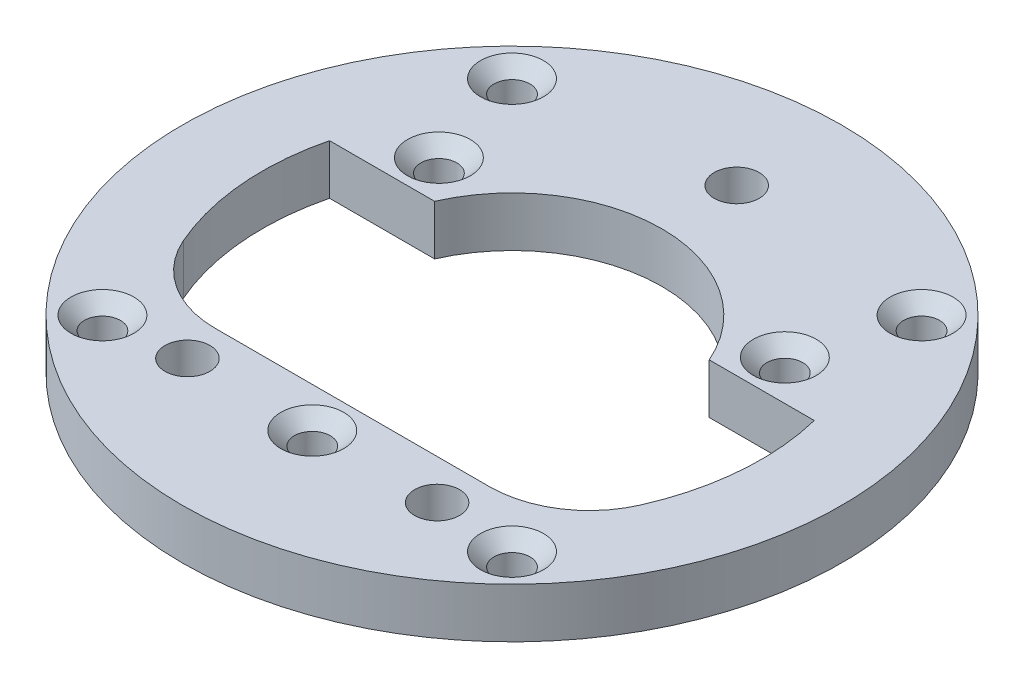
SolidWorks part; units mm, degrees
material "ABS"
ref_plane "Front Plane" through (0, 0, 0) normal (0, 0, 1) x (1, 0, 0)
ref_plane "Top Plane" through (0, 0, 0) normal (0, 1, 0) x (1, 0, 0)
ref_plane "Right Plane" through (0, 0, 0) normal (1, 0, 0) x (0, 0, -1)
sketch "Sketch1" plane through (0, 0, 0) normal (0, 1, 0) x (1, 0, 0)
  circle A0 centre (0, 0) radius 33
  circle A1 centre (0, 0) radius 25
  dimension "D1" = 66
  dimension "D2" = 8
extrude "Boss-Extrude1" add sketch "Sketch1" along normal blind 5
sketch "Sketch2" plane through (0, 5, 0) normal (0, 1, 0) x (1, 0, 0)
  line L0 (-19.2094, -16) -> (19.2094, -16)
  line L1 (-24.2693, 6) -> (-13.7477, 6)
  line L2 (0, 0) -> (7.7557, 0) construction
  line L3 (13.7477, 6) -> (24.2693, 6)
  line L4 (-20.5061, 20.5061) -> (0, 0) construction
  circle A0 centre (0, 22.5) radius 2.25 construction
  circle A1 centre (-12.5, -20) radius 2.25 construction
  circle A2 centre (12.5, -20) radius 2.25 construction
  circle A3 centre (0, -20) radius 1.5 construction
  circle A4 centre (0, 0) radius 20 construction
  circle A5 centre (-17.3205, 10) radius 1.5 construction
  circle A6 centre (0, 0) radius 25 construction
  circle A7 centre (17.3205, 10) radius 1.5 construction
  arc A8 (-13.7477, 6) -> (13.7477, 6) centre (0, 0) cw
  arc A9 (24.2693, 6) -> (-24.2882, 5.9232) centre (0, 0) ccw
  arc A10 (19.2094, -16) -> (-19.2094, -16) centre (0, 0) cw
  circle A12 centre (0, 0) radius 29 construction
  circle A13 centre (0, 0) radius 33 construction
  circle A14 centre (-20.5061, 20.5061) radius 1.75 construction
  circle A15 centre (20.5061, 20.5061) radius 1.75 construction
  circle A16 centre (20.5061, -20.5061) radius 1.75 construction
  circle A17 centre (-20.5061, -20.5061) radius 1.75 construction
  point P19 (0, 0)
  point P44 (0, 0)
  circle M2 centre (0, 0) radius 25
  dimension "D5" = 4.5
  dimension "D6" = 4.5
  dimension "D7" = 4.5
  dimension "D10" = 3
  dimension "D12" = 15
  dimension "D16" = 3.5
  dimension "D1" = 25
  dimension "D2" = 12.5
  dimension "D3" = 22.5
  dimension "D4" = 20
  dimension "D9" = 5
  dimension "D11" = 4
  dimension "D13" = 4
  dimension "D14" = 4
  dimension "D15" = 135
  dimension "D18" = 5
  dimension "D8" = 3
  dimension "D17" = 4
extrude "Saliente-Extruir1" add sketch "Sketch2" against normal up to surface (5 mm away) contours L1 A8 L3 M2 | L0 M2 region at (0, 5, 19.6621) region at (0, 5, -15.401) up to face at (0, 0, 33)
sketch "Croquis1" plane through (0, 5, 0) normal (0, 1, 0) x (1, 0, 0)
  circle A0 centre (-20.5061, 20.5061) radius 1.75 construction
  circle A1 centre (-20.5061, 20.5061) radius 1.75
  circle A2 centre (0, 22.5) radius 2.25 construction
  circle A3 centre (0, 22.5) radius 2.25
  circle A4 centre (20.5061, 20.5061) radius 1.75 construction
  circle A5 centre (20.5061, 20.5061) radius 1.75
  circle A6 centre (-17.3205, 10) radius 1.5 construction
  circle A7 centre (-17.3205, 10) radius 1.5
  circle A8 centre (17.3205, 10) radius 1.5 construction
  circle A9 centre (17.3205, 10) radius 1.5
  circle A10 centre (0, -20) radius 1.5 construction
  circle A11 centre (0, -20) radius 1.5
  circle A12 centre (12.5, -20) radius 2.25 construction
  circle A13 centre (12.5, -20) radius 2.25
  circle A14 centre (-12.5, -20) radius 2.25 construction
  circle A15 centre (-12.5, -20) radius 2.25
  circle A16 centre (-20.5061, -20.5061) radius 1.75 construction
  circle A17 centre (-20.5061, -20.5061) radius 1.75
  circle A18 centre (20.5061, -20.5061) radius 1.75 construction
  circle A19 centre (20.5061, -20.5061) radius 1.75
extrude "Cortar-Extruir1" cut sketch "Croquis1" against normal up to next
fillet "Redondeo1" radius 10 2 edges at (19.2094, 2.5, 16) (-19.2094, 2.5, 16)
hole_wizard "CSK for M3 Flat Head Machine Screw1" positions "Sketch4" profile "Sketch5" countersink size "M3" standard "ANSI Metric" end condition through all
sketch "Sketch4" plane through (0, 5, 0) normal (0, 1, 0) x (1, 0, 0)
  point P0 (-20.5061, 20.5061)
  point P3 (20.5061, 20.5061)
  point P6 (20.5061, -20.5061)
  point P9 (-20.5061, -20.5061)
sketch "Sketch5" plane through (-20.5061, 5, -20.5061) normal (1, 0, 0) x (0, 0, 1)
  line L0 (0, 0) -> (0, 5)
  line L1 (0, 5) -> (1.8, 5)
  line L2 (1.8, 5) -> (1.8, 1.35)
  line L3 (1.8, 1.35) -> (3.15, 0)
  line L5 (3.15, 0) -> (0, 0)
  line L6 (-1.8, 1.35) -> (-3.15, 0) construction
  line L11 (0, -6.35) -> (0, 107.95) construction
  dimension "Thru Hole Dia." = 3.6
  dimension "Thru Hole Depth" = 5
  dimension "Near C'Sink Dia." = 6.3
  dimension "Near C'Sink Angle" = 90
hole_wizard "CSK for M3 Flat Head Machine Screw2" positions "Sketch6" profile "Sketch7" countersink size "M3" standard "ANSI Metric" end condition through all
sketch "Sketch6" plane through (0, 5, 0) normal (0, 1, 0) x (1, 0, 0)
  point P0 (-17.3205, 10)
  point P3 (17.3205, 10)
  point P6 (0, -20)
sketch "Sketch7" plane through (-17.3205, 5, -10) normal (1, 0, 0) x (0, 0, 1)
  line L0 (0, 0) -> (0, 5)
  line L1 (0, 5) -> (1.8, 5)
  line L2 (1.8, 5) -> (1.8, 1.35)
  line L3 (1.8, 1.35) -> (3.15, 0)
  line L5 (3.15, 0) -> (0, 0)
  line L6 (-1.8, 1.35) -> (-3.15, 0) construction
  line L11 (0, -6.35) -> (0, 107.95) construction
  dimension "Thru Hole Dia." = 3.6
  dimension "Thru Hole Depth" = 5
  dimension "Near C'Sink Dia." = 6.3
  dimension "Near C'Sink Angle" = 90
equation "\"D2@Sketch2\"=\"D1@Sketch2\"/2"
equation "\"D6@Sketch2\"=\"D5@Sketch2\""
equation "\"D7@Sketch2\"=\"D6@Sketch2\""
equation "\"D10@Sketch2\"=\"D8@Sketch2\""
